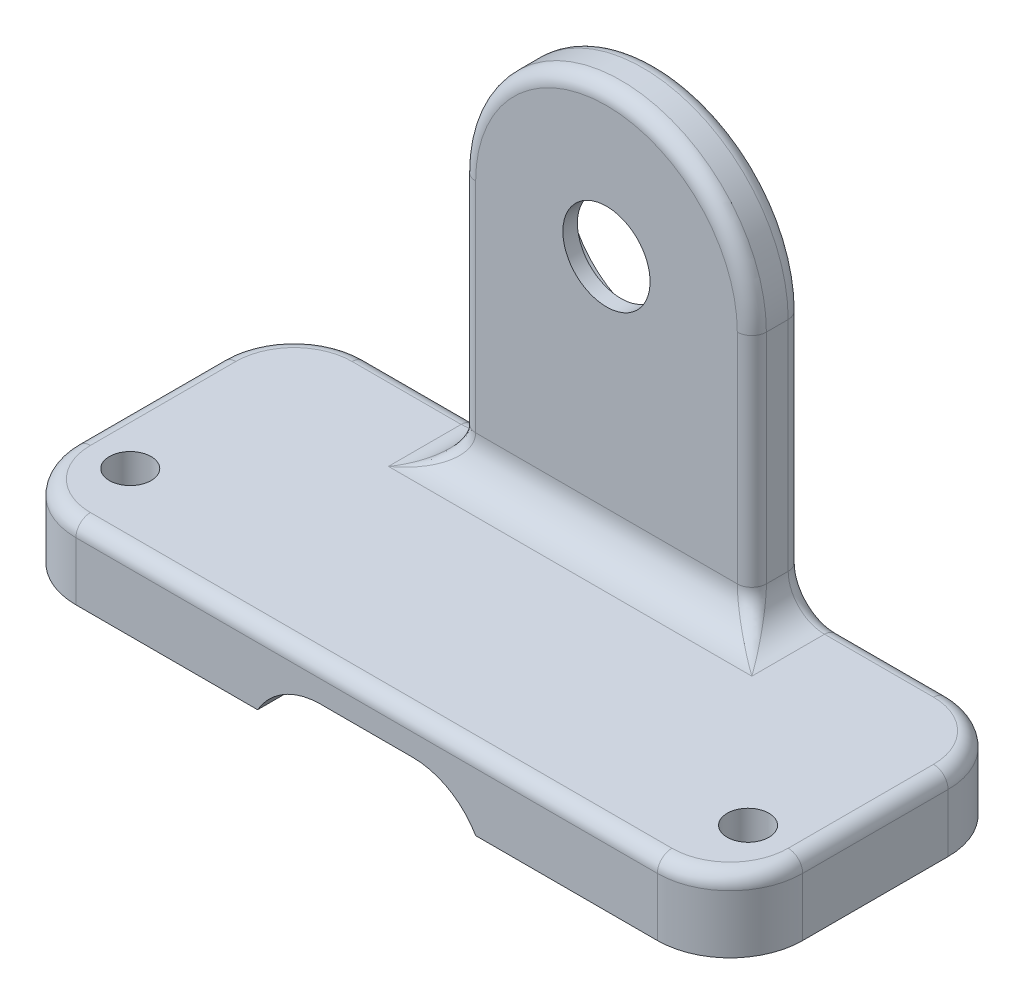
SolidWorks part; units mm, degrees
ref_plane "Спереди" through (0, 0, 0) normal (0, 0, 1) x (1, 0, 0)
ref_plane "Сверху" through (0, 0, 0) normal (0, 1, 0) x (1, 0, 0)
ref_plane "Справа" through (0, 0, 0) normal (1, 0, 0) x (0, 0, -1)
sketch "Эскиз1" plane through (0, 0, 0) normal (0, 1, 0) x (1, 0, 0)
  line L1 (0, 0) -> (-100, 0)
  line L2 (0, 0) -> (0, 40)
  line L3 (0, 40) -> (-100, 40)
  line L4 (-100, 0) -> (-100, 40)
  dimension "D1" = 100
  dimension "D2" = 40
extrude "Бобышка-Вытянуть1" add sketch "Эскиз1" along normal blind 10
sketch "Эскиз2" plane through (0, 0, -40) normal (0, 0, -1) x (-1, 0, 0)
  line L0 (50, 10) -> (50, 45) construction
  line L1 (0, 10) -> (100, 10) construction
  line L2 (30, 10) -> (30, 45)
  line L3 (70, 10) -> (70, 45)
  line L4 (100, 10) -> (70, 10)
  line L8 (0, 0) -> (100, 0)
  line L9 (100, 0) -> (100, 10)
  line L10 (100, 10) -> (0, 10)
  line L11 (0, 10) -> (0, 0)
  line L12 (0, 0) -> (100, 0)
  line L13 (100, 0) -> (100, 10)
  line L14 (30, 10) -> (0, 10)
  line L15 (0, 10) -> (0, 0)
  arc A0 (70, 45) -> (30, 45) centre (50, 45) ccw
  point P9 (50, 46.0026)
  point P10 (50, 42.9668)
  point P11 (50, 45.1626)
  point P12 (50, 45.0866)
  dimension "D1" = 20
  dimension "D2" = 35
  dimension "D3" = 0
extrude "Бобышка-Вытянуть2" add sketch "Эскиз2" against normal blind 7
sketch "Эскиз3" plane through (0, 0, -40) normal (0, 0, -1) x (-1, 0, 0)
  circle A0 centre (50, 45) radius 12.5
  dimension "D1" = 25
extrude "Вырез-Вытянуть1" cut sketch "Эскиз3" against normal blind 5
sketch "Эскиз4" plane through (0, 0, -35) normal (0, 0, -1) x (-1, 0, 0)
  circle A0 centre (50, 45) radius 6
  dimension "D1" = 12
extrude "Вырез-Вытянуть2" cut sketch "Эскиз4" against normal through all
sketch "Эскиз5" plane through (0, 0, -40) normal (0, 0, -1) x (-1, 0, 0)
  line L0 (50, 32.5) -> (50, 0) construction
  line L1 (0, 0) -> (100, 0) construction
  line L3 (65, 5) -> (35, 5)
  line L4 (65, 5) -> (65, 0)
  line L5 (65, 0) -> (35, 0)
  line L6 (35, 5) -> (35, 0)
  circle A0 centre (50, 45) radius 12.5 construction
  dimension "D1" = 5
  dimension "D2" = 30
extrude "Вырез-Вытянуть3" cut sketch "Эскиз5" against normal through all
sketch "Эскиз7" plane through (0, 10, 0) normal (0, 1, 0) x (1, 0, 0)
  circle A0 centre (-92.5032, 9.9781) radius 2.8716
extrude "Вырез-Вытянуть4" cut sketch "Эскиз7" against normal through all
ref_plane "Плоскость2" through (-50, 0, 0) normal (-1, 0, 0) x (0, 0, 1)
mirror "Зеркальное отражение1" about plane through (-50, 0, 0) normal (-1, 0, 0) of "Вырез-Вытянуть4"
fillet "Скругление1" radius 10 6 edges at (0, 5, 0) (0, 5, -40) (-100, 5, -40) (-100, 5, 0) (-35, 5, -20) (-65, 5, -20)
fillet "Скругление4" radius 5 3 edges at (-70, 10, -36.5) (-30, 10, -36.5) (-50, 10, -33)
fillet "Скругление8" radius 2 14 edges at (-71.4645, 11.4645, -40) (-82.5, 10, -40) (-97.0711, 10, -37.0711) (-100, 10, -20) (-97.0711, 10, -2.9289) (-50, 10, 0) (-2.9289, 10, -2.9289) (0, 10, -20) (-2.9289, 10, -37.0711) (-17.5, 10, -40) (-28.5355, 11.4645, -40) (-30, 30, -40) (-50, 65, -40) (-70, 30, -40)
fillet "Скругление9" radius 2 5 edges at (-71.4645, 11.4645, -31.5355) (-28.5355, 11.4645, -31.5355) (-30, 30, -33) (-50, 65, -33) (-70, 30, -33)
